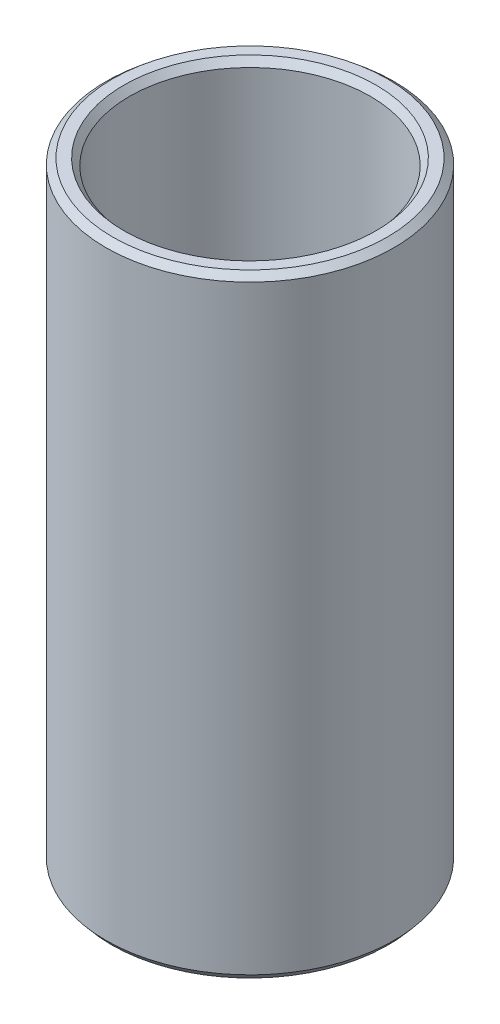
SolidWorks part; units mm, degrees
ref_plane "Front Plane" through (0, 0, 0) normal (0, 0, 1) x (1, 0, 0)
ref_plane "Top Plane" through (0, 0, 0) normal (0, 1, 0) x (1, 0, 0)
ref_plane "Right Plane" through (0, 0, 0) normal (1, 0, 0) x (0, 0, -1)
sketch "Sketch1" plane through (0, 0, 0) normal (0, 1, 0) x (1, 0, 0)
  circle A0 centre (0, 0) radius 47.5
  dimension "SLEEVE_OD" = 95
extrude "Boss-Extrude1" add sketch "Sketch1" along normal blind 201.9879
sketch "Sketch2" plane through (0, 0, 0) normal (0, 1, 0) x (1, 0, 0)
  circle A0 centre (0, 0) radius 39.7066
  dimension "BORE_D" = 79.4132
extrude "Cut-Extrude1" cut sketch "Sketch2" along normal through all
chamfer "Chamfer1" distance 1.8979 angle 49.808 4 edges at (0, 201.9879, 39.7066) (0, 0, 39.7066) (0, 0, 47.5) (0, 201.9879, 47.5) first distance on face at (0, 201.9879, 39.7066) first distance on face at (0, 0, 39.7066) first distance on face at (0, 201.9879, 47.5)
